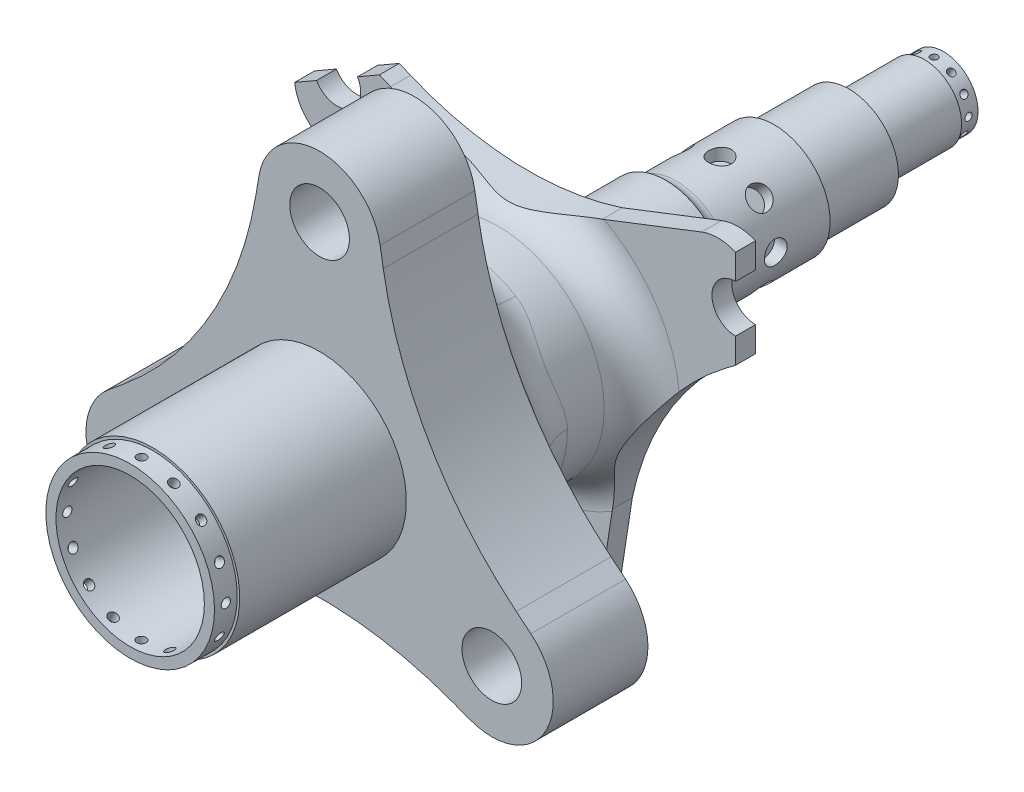
SolidWorks part; units mm, degrees
ref_plane "Front Plane" through (0, 0, 0) normal (0, 0, 1) x (1, 0, 0)
ref_plane "Top Plane" through (0, 0, 0) normal (0, 1, 0) x (1, 0, 0)
ref_plane "Right Plane" through (0, 0, 0) normal (1, 0, 0) x (0, 0, -1)
sketch "Sketch1" plane through (0, 0, 0) normal (0, 0, 1) x (1, 0, 0)
  circle A0 centre (0, 0) radius 10
  dimension "D1" = 20
extrude "IB mount" add sketch "Sketch1" along normal mid plane 15
ref_plane "OB midplane" through (0, 0, 36.83) normal (0, 0, 1) x (1, 0, 0)
sketch "Sketch2" plane through (0, 0, 36.83) normal (0, 0, 1) x (1, 0, 0)
  circle A0 centre (0, 0) radius 12.5
  dimension "D1" = 25
extrude "OB mount" add sketch "Sketch2" along normal mid plane 15 separate body contours A0
ref_plane "Rotor midplane" through (0, 0, 53.34) normal (0, 0, 1) x (1, 0, 0)
sketch "Sketch4" plane through (0, 0, 53.34) normal (0, 0, 1) x (1, 0, 0)
  circle A0 centre (0, 0) radius 82.55
  dimension "D1" = 165.1
extrude "Boss-Extrude3" add sketch "Sketch4" along normal mid plane 4 separate body contours A0
ref_plane "Wheel Center Midplane" through (0, 0, 89.408) normal (0, 0, 1) x (1, 0, 0)
sketch "Sketch5" plane through (0, 0, 89.408) normal (0, 0, 1) x (1, 0, 0)
  line L0 (-19.4328, 52.35) -> (18.1305, 52.35) construction
  line L1 (-19.4328, 46) -> (18.1305, 46) construction
  circle A0 centre (0, 0) radius 52.35
  circle A1 centre (0, 40) radius 6
  circle A2 centre (20, 34.641) radius 6
  circle A3 centre (34.641, 20) radius 6
  circle A4 centre (40, 0) radius 6
  circle A5 centre (34.641, -20) radius 6
  circle A6 centre (20, -34.641) radius 6
  circle A7 centre (0, -40) radius 6
  circle A8 centre (-20, -34.641) radius 6
  circle A9 centre (-34.641, -20) radius 6
  circle A10 centre (-40, 0) radius 6
  circle A11 centre (-34.641, 20) radius 6
  circle A12 centre (-20, 34.641) radius 6
  point P29 (0, 0)
  dimension "D3" = 12
  dimension "D2" = 40
  dimension "D4" = 6.35
  dimension "D1" = 12
extrude "Boss-Extrude4" add sketch "Sketch5" along normal mid plane 19.05 separate body contours A0 A12 A11 A10 A9 A8 A7 A6 A5 A4 A3 A2 A1 | A12 | A1 | A2 | A3 | A4 | A5 | A6 | A7 | A8 | A9 | A10 | A11 region at (0, 0, 89.408) region at (0, 40, 89.408) region at (20, 34.641, 89.408) region at (34.641, 20, 89.408) region at (40, 0, 89.408) region at (34.641, -20, 89.408) region at (20, -34.641, 89.408) region at (0, -40, 89.408) region at (-20, -34.641, 89.408) region at (-34.641, -20, 89.408) region at (-40, 0, 89.408) region at (-34.641, 20, 89.408) region at (-20, 34.641, 89.408)
extrude "Cut-Extrude2" cut sketch "Sketch5<5>" against normal blind 19.05 from surface contours A1 | A5 | A9 starting at face at (52.35, 0, 98.933)
sketch "Sketch5<5>" plane through (0, 0, 89.408) normal (0, 0, 1) x (1, 0, 0) same geometry as "Sketch5"
sketch "Sketch8" plane through (0, 0, 98.933) normal (0, 0, 1) x (1, 0, 0)
  circle A0 centre (0, 0) radius 17.4625
  dimension "D1" = 34.925
extrude "Boss-Extrude5" add sketch "Sketch8" along normal blind 38.1
sketch "Sketch9" plane through (0, 0, 137.033) normal (0, 0, 1) x (1, 0, 0)
  circle A0 centre (0, 0) radius 14.9225
  dimension "D1" = 29.845
sketch "Sketch10" plane through (0, 0, 29.33) normal (0, 0, -1) x (-1, 0, 0)
  circle A2 centre (0, 0) radius 11.25
  circle A3 centre (0, 0) radius 11.25
  dimension "D1" = 1.25
extrude "Boss-Extrude6" add sketch "Sketch10" along normal up to surface (21.83 mm away) up to face at (10, 0, 7.5)
sketch "Sketch11" plane through (0, 0, 0) normal (0, 1, 0) x (1, 0, 0)
  line L2 (11.25, -7.5) -> (-11.25, -7.5) construction
  line L3 (11.25, -7.5) -> (-11.25, -7.5) construction
  line L4 (0, -29.33) -> (0, -7.5) construction
  line L6 (12.5, -29.33) -> (-12.5, -29.33) construction
  line L7 (12.5, -29.33) -> (-12.5, -29.33) construction
  circle A0 centre (0, -18.415) radius 2.286
  dimension "D1" = 4.572
ref_plane "WS sensor plane" through (0, 11.25, 0) normal (0, 1, 0) x (1, 0, 0)
sketch "Sketch12" plane through (0, 11.25, 0) normal (0, 1, 0) x (1, 0, 0)
  circle A0 centre (0, -18.415) radius 2.286
  circle A1 centre (0, -18.415) radius 2.286 construction
extrude "Cut-Extrude4" cut sketch "Sketch12" against normal blind 2.54 contours A0
pattern_circular "CirPattern1" count 8 over 360 about axis through (0, 0, -7.5) along (0, 0, -1) of "Cut-Extrude4"
sketch "Sketch15" plane through (0, 0, 79.883) normal (0, 0, -1) x (-1, 0, 0)
  circle A2 centre (0, 0) radius 21.2725
  circle A3 centre (0, 0) radius 21.2725
  dimension "D1" = 3.81
extrude "Boss-Extrude7" add sketch "Sketch15" along normal up to surface (24.543 mm away) contours A3 up to face at (82.55, 0, 55.34)
extrude "Cut-Extrude5" cut sketch "Sketch9" against normal up to surface (47.625 mm away) contours A0 up to plane "Wheel Center Midplane"
sketch "Sketch16" plane through (0, 0, 44.33) normal (0, 0, 1) x (1, 0, 0)
  circle A2 centre (0, 0) radius 15
  circle A3 centre (0, 0) radius 15
  dimension "D1" = 2.5
extrude "Boss-Extrude8" add sketch "Sketch16" along normal up to surface (7.01 mm away) up to face at (82.55, 0, 51.34)
fillet "Fillet4" radius 3.81 1 edges at (15, 0, 51.34)
sketch "Sketch17" plane through (0, 0, -7.5) normal (0, 0, -1) x (-1, 0, 0)
  circle A3 centre (0, 0) radius 7.46
  circle A4 centre (0, 0) radius 7.46
  dimension "D2" = 14.92
  dimension "D1" = 2.54
extrude "Boss-Extrude9" add sketch "Sketch17" along normal blind 19.05 contours A4
sketch "Sketch18" plane through (0, 0, -26.55) normal (0, 0, -1) x (-1, 0, 0)
  circle A2 centre (0, 0) radius 4.92
  circle A3 centre (0, 0) radius 4.92
  dimension "D1" = 2.54
extrude "Cut-Extrude6" cut sketch "Sketch18" against normal blind 3.81
sketch "Sketch19" plane through (0, 0, -26.55) normal (0, 0, -1) x (-1, 0, 0)
  circle A1 centre (0, 0) radius 7.46
  circle A2 centre (0, 0) radius 6.96
  circle A3 centre (0, 0) radius 6.96
  dimension "D1" = 0.5
extrude "Cut-Extrude7" cut sketch "Sketch19" against normal up to surface (3.81 mm away) up to face at (-4.92, 0, -22.74)
ref_plane "Plane5" through (0, 6.96, 0) normal (0, 1, 0) x (1, 0, 0)
sketch "Sketch20" plane through (0, 6.96, 0) normal (0, 1, 0) x (1, 0, 0)
  line L0 (6.96, 26.55) -> (-6.96, 26.55) construction
  line L1 (6.96, 26.55) -> (-6.96, 26.55) construction
  line L2 (6.96, 22.74) -> (-6.96, 22.74) construction
  line L3 (6.96, 22.74) -> (-6.96, 22.74) construction
  line L4 (0, 22.74) -> (0, 26.55) construction
  circle A0 centre (0, 24.645) radius 0.7319
extrude "Cut-Extrude8" cut sketch "Sketch20" against normal up to surface and the other way through all up to face at (-4.92, 0, -22.74)
pattern_circular "CirPattern2" count 12 over 360 about axis through (0, 0, -26.55) along (0, 0, -1) of "Cut-Extrude8"
sketch "Sketch21" plane through (0, 0, 137.033) normal (0, 0, 1) x (1, 0, 0)
  circle A1 centre (0, 0) radius 17.4625
  circle A2 centre (0, 0) radius 16.9625
  circle A3 centre (0, 0) radius 16.9625
  circle M3 centre (0, 0) radius 17.4625
  dimension "D1" = 0.5
extrude "Cut-Extrude9" cut sketch "Sketch21" against normal blind 4.572 contours A3 M3 region at (-16.9686, 0, 137.033)
sketch "Sketch22" plane through (0, 0, 0) normal (0, 1, 0) x (1, 0, 0)
  line L0 (-16.9625, -137.033) -> (16.9625, -137.033) construction
  line L1 (-16.9625, -132.461) -> (16.9625, -132.461) construction
  line L2 (-16.9625, -137.033) -> (16.9625, -137.033) construction
  line L3 (-16.9625, -132.461) -> (16.9625, -132.461) construction
  line L4 (0, -132.461) -> (0, -137.033) construction
  circle A0 centre (0, -134.747) radius 0.9339
extrude "Cut-Extrude10" cut sketch "Sketch22" against normal up to surface (16.9625 mm away) up to face at (16.9625, 0, 132.461)
pattern_circular "CirPattern3" count 16 over 360 about axis through (0, 0, 137.033) along (0, 0, 1) of "Cut-Extrude10"
sketch "Brakes Rough Diagram" plane through (0, 0, 51.34) normal (0, 0, -1) x (-1, 0, 0)
  line L0 (-31.719, 82.55) -> (31.719, 82.55) construction
  line L5 (-22.9, 82.05) -> (22.9, 82.05)
  line L6 (-22.9, 82.05) -> (-22.9, 53.55)
  line L7 (-22.9, 53.55) -> (22.9, 53.55)
  line L8 (22.9, 82.05) -> (22.9, 53.55)
  line L9 (-31.719, 53.05) -> (31.719, 53.05) construction
  line L10 (-31.719, 51.05) -> (31.719, 51.05) construction
  line L11 (-22.9, 82.05) -> (22.9, 53.55) construction
  line L12 (-22.9, 53.55) -> (22.9, 82.05) construction
  circle A0 centre (0, 0) radius 53.05 construction
  circle A1 centre (0, 0) radius 82.55 construction
  circle A2 centre (0, 46.2875) radius 4.7625
  point P16 (0, 67.8)
  point P17 (0, 67.8)
  point P22 (0, 51.05)
  point P24 (0, 53.55)
  point P25 (0, 53.05)
  dimension "D6" = 9.525
  dimension "D1" = 28.5
  dimension "D2" = 45.8
  dimension "D3" = 0.5
  dimension "D4" = 0.5
  dimension "D5" = 2
sketch "Sketch28" plane through (0, 0, 51.34) normal (0, 0, -1) x (-1, 0, 0)
  circle A0 centre (0, 46.2875) radius 4.7625 construction
  circle A1 centre (0, 46.2875) radius 4.7625
  circle A2 centre (23.1437, 40.0862) radius 4.7625
  circle A3 centre (40.0862, 23.1438) radius 4.7625
  circle A4 centre (46.2875, 0) radius 4.7625
  circle A5 centre (40.0862, -23.1437) radius 4.7625
  circle A6 centre (23.1438, -40.0862) radius 4.7625
  circle A7 centre (0, -46.2875) radius 4.7625
  circle A8 centre (-23.1437, -40.0862) radius 4.7625
  circle A9 centre (-40.0862, -23.1438) radius 4.7625
  circle A10 centre (-46.2875, 0) radius 4.7625
  circle A11 centre (-40.0862, 23.1437) radius 4.7625
  circle A12 centre (-23.1438, 40.0862) radius 4.7625
  circle A13 centre (0, 0) radius 53.05 construction
  circle A14 centre (0, 0) radius 53.05
  circle A16 centre (0, 0) radius 82.55
  circle A17 centre (0, 0) radius 82.55
  point P27 (0, 0)
  circle M6 centre (0, 0) radius 82.55
  dimension "D2" = 0
  dimension "D1" = 12
extrude "Cut-Extrude11" cut sketch "Sketch28" along direction (0, 0, 1) on the side against the normal up to surface (4 mm away) contours A14 M6 | A3 | A11 | A7 region at (-40.0862, 23.1438, 51.34) region at (0, -46.2875, 51.34) region at (40.0862, 23.1437, 51.34) region at (80.2151, 0, 51.34) up to face at (21.2725, 0, 55.34)
sketch "Brake Rotor Mount Points" plane through (0, 0, 51.34) normal (0, 0, -1) x (-1, 0, 0)
  line L0 (-4.7625, 46.2875) -> (4.7625, 46.2875) construction
  line L1 (-4.1244, 43.9062) -> (4.1244, 48.6688) construction
  line L2 (0, 51.05) -> (0, 41.525) construction
  line L3 (4.1244, 48.6688) -> (8.5239, 51.2088)
  line L4 (-4.1244, 43.9062) -> (-8.5239, 41.3662)
  line L5 (18.3812, 40.0862) -> (27.9062, 40.0862) construction
  line L6 (19.0193, 42.4674) -> (27.2682, 37.7049) construction
  line L7 (25.525, 44.2106) -> (20.7625, 35.9617) construction
  line L8 (27.9062, 40.0862) -> (32.9862, 40.0862)
  line L9 (18.3812, 40.0862) -> (13.3012, 40.0862)
  line L10 (35.9617, 25.525) -> (44.2106, 20.7625) construction
  line L11 (37.7049, 27.2682) -> (42.4674, 19.0193) construction
  line L12 (44.2106, 25.525) -> (35.9617, 20.7625) construction
  line L13 (44.2106, 20.7625) -> (48.61, 18.2225)
  line L14 (35.9617, 25.525) -> (31.5623, 28.065)
  line L15 (43.9062, 4.1244) -> (48.6688, -4.1244) construction
  line L16 (46.2875, 4.7625) -> (46.2875, -4.7625) construction
  line L17 (51.05, 0) -> (41.525, 0) construction
  line L18 (48.6688, -4.1244) -> (51.2088, -8.5239)
  line L19 (43.9062, 4.1244) -> (41.3662, 8.5239)
  line L20 (40.0862, -18.3812) -> (40.0862, -27.9062) construction
  line L21 (42.4674, -19.0193) -> (37.7049, -27.2682) construction
  line L22 (44.2106, -25.525) -> (35.9617, -20.7625) construction
  line L23 (40.0862, -27.9062) -> (40.0862, -32.9862)
  line L24 (40.0862, -18.3812) -> (40.0862, -13.3012)
  line L25 (25.525, -35.9617) -> (20.7625, -44.2106) construction
  line L26 (27.2682, -37.7049) -> (19.0193, -42.4674) construction
  line L27 (25.525, -44.2106) -> (20.7625, -35.9617) construction
  line L28 (20.7625, -44.2106) -> (18.2225, -48.61)
  line L29 (25.525, -35.9617) -> (28.065, -31.5623)
  line L30 (4.1244, -43.9062) -> (-4.1244, -48.6688) construction
  line L31 (4.7625, -46.2875) -> (-4.7625, -46.2875) construction
  line L32 (0, -51.05) -> (0, -41.525) construction
  line L33 (-4.1244, -48.6688) -> (-8.5239, -51.2088)
  line L34 (4.1244, -43.9062) -> (8.5239, -41.3662)
  line L35 (-18.3812, -40.0862) -> (-27.9062, -40.0862) construction
  line L36 (-19.0193, -42.4674) -> (-27.2682, -37.7049) construction
  line L37 (-25.525, -44.2106) -> (-20.7625, -35.9617) construction
  line L38 (-27.9062, -40.0862) -> (-32.9862, -40.0862)
  line L39 (-18.3812, -40.0862) -> (-13.3012, -40.0862)
  line L40 (-35.9617, -25.525) -> (-44.2106, -20.7625) construction
  line L41 (-37.7049, -27.2682) -> (-42.4674, -19.0193) construction
  line L42 (-44.2106, -25.525) -> (-35.9617, -20.7625) construction
  line L43 (-44.2106, -20.7625) -> (-48.61, -18.2225)
  line L44 (-35.9617, -25.525) -> (-31.5623, -28.065)
  line L45 (-43.9062, -4.1244) -> (-48.6688, 4.1244) construction
  line L46 (-46.2875, -4.7625) -> (-46.2875, 4.7625) construction
  line L47 (-51.05, 0) -> (-41.525, 0) construction
  line L48 (-48.6688, 4.1244) -> (-51.2088, 8.5239)
  line L49 (-43.9062, -4.1244) -> (-41.3662, -8.5239)
  line L50 (-40.0862, 18.3812) -> (-40.0862, 27.9062) construction
  line L51 (-42.4674, 19.0193) -> (-37.7049, 27.2682) construction
  line L52 (-44.2106, 25.525) -> (-35.9617, 20.7625) construction
  line L53 (-40.0862, 27.9062) -> (-40.0862, 32.9862)
  line L54 (-40.0862, 18.3812) -> (-40.0862, 13.3012)
  line L55 (-25.525, 35.9617) -> (-20.7625, 44.2106) construction
  line L56 (-27.2682, 37.7049) -> (-19.0193, 42.4674) construction
  line L57 (-25.525, 44.2106) -> (-20.7625, 35.9617) construction
  line L58 (-20.7625, 44.2106) -> (-18.2225, 48.61)
  line L59 (-25.525, 35.9617) -> (-28.065, 31.5623)
  circle A1 centre (23.1438, -40.0862) radius 4.7625
  circle A2 centre (23.1438, -40.0862) radius 4.7625 construction
  circle A3 centre (40.0862, -23.1437) radius 4.7625
  circle A4 centre (40.0862, -23.1437) radius 4.7625 construction
  circle A5 centre (46.2875, 0) radius 4.7625
  circle A6 centre (46.2875, 0) radius 4.7625 construction
  circle A7 centre (40.0862, 23.1438) radius 4.7625
  circle A8 centre (40.0862, 23.1438) radius 4.7625 construction
  circle A9 centre (23.1437, 40.0862) radius 4.7625
  circle A10 centre (23.1437, 40.0862) radius 4.7625 construction
  circle A11 centre (0, 46.2875) radius 4.7625
  circle A12 centre (0, 46.2875) radius 4.7625 construction
  circle A13 centre (0, 0) radius 53.05
  circle A14 centre (0, 0) radius 53.05 construction
  circle A15 centre (-23.1438, 40.0862) radius 4.7625
  circle A16 centre (-23.1438, 40.0862) radius 4.7625 construction
  circle A17 centre (-40.0862, 23.1437) radius 4.7625
  circle A18 centre (-40.0862, 23.1437) radius 4.7625 construction
  circle A19 centre (-46.2875, 0) radius 4.7625
  circle A20 centre (-46.2875, 0) radius 4.7625 construction
  circle A21 centre (-40.0862, -23.1438) radius 4.7625
  circle A22 centre (-40.0862, -23.1438) radius 4.7625 construction
  circle A23 centre (-23.1437, -40.0862) radius 4.7625
  circle A24 centre (-23.1437, -40.0862) radius 4.7625 construction
  circle A25 centre (0, -46.2875) radius 4.7625
  circle A26 centre (0, -46.2875) radius 4.7625 construction
  circle A27 centre (0, 0) radius 82.55
  circle A28 centre (0, 0) radius 82.55 construction
  point P140 (0, 0)
  dimension "D15" = 60
  dimension "D17" = 5.08
  dimension "D1" = 0
  dimension "D2" = 0
  dimension "D3" = 0
  dimension "D4" = 0
  dimension "D5" = 0
  dimension "D6" = 0
  dimension "D7" = 0
  dimension "D8" = 0
  dimension "D9" = 0
  dimension "D10" = 0
  dimension "D11" = 0
  dimension "D12" = 0
  dimension "D13" = 0
  dimension "D14" = 0
  dimension "D16" = 12
sketch "Sketch30" plane through (0, 0, 51.34) normal (0, 0, -1) x (-1, 0, 0)
  line L0 (-4.1244, -48.6688) -> (-8.5239, -51.2088) construction
  line L1 (4.1244, -43.9062) -> (8.5239, -41.3662) construction
  line L2 (35.9617, 25.525) -> (31.5623, 28.065) construction
  line L3 (44.2106, 20.7625) -> (48.61, 18.2225) construction
  line L4 (-40.0862, 18.3812) -> (-40.0862, 13.3012) construction
  line L5 (-40.0862, 27.9062) -> (-40.0862, 32.9862) construction
  line L6 (-4.1244, -48.6688) -> (-8.5239, -51.2088)
  line L7 (4.1244, -43.9062) -> (8.5239, -41.3662)
  line L8 (35.9617, 25.525) -> (31.5623, 28.065)
  line L9 (44.2106, 20.7625) -> (48.61, 18.2225)
  line L10 (-40.0862, 18.3812) -> (-40.0862, 13.3012)
  line L11 (-40.0862, 27.9062) -> (-40.0862, 32.9862)
  line L12 (-40.0862, 13.3012) -> (-18.5757, -2.9599)
  line L13 (-33.2561, 33.0986) -> (6.7245, 17.5669)
  line L14 (45.2923, 12.2513) -> (11.8512, -14.607)
  line L15 (31.5623, 28.065) -> (6.7245, 17.5669)
  line L16 (-12.0362, -45.3499) -> (-18.5757, -2.9599)
  line L17 (8.5239, -41.3662) -> (11.8512, -14.607)
  line L18 (-12.0362, -45.3499) -> (-18.5757, -2.9599)
  line L19 (-33.2561, 33.0986) -> (6.7245, 17.5669)
  circle A0 centre (0, -46.2875) radius 4.7625 construction
  circle A1 centre (40.0862, 23.1438) radius 4.7625 construction
  circle A2 centre (-40.0862, 23.1437) radius 4.7625 construction
  circle A3 centre (0, -46.2875) radius 4.7625
  circle A4 centre (40.0862, 23.1438) radius 4.7625
  circle A5 centre (-40.0862, 23.1437) radius 4.7625
  arc A6 (-40.0862, 32.9862) -> (-33.2561, 33.0986) centre (-36.5332, 24.6629) cw
  circle A7 centre (0, 0) radius 18.81 construction
  arc A8 (48.61, 18.2225) -> (45.2923, 12.2513) centre (39.6253, 19.3073) cw
  arc A9 (-8.5239, -51.2088) -> (-12.0362, -45.3499) centre (-3.092, -43.9701) cw
  circle A10 centre (0, 0) radius 53.05 construction
  circle A11 centre (0, 0) radius 53.05
  arc A12 (8.825, -38.9441) -> (28.5717, -1.1779) centre (69.1617, -46.4466) cw
  arc A13 (-38.1391, 11.8294) -> (-15.3059, -24.1549) centre (-74.8047, -36.6725) cw
  arc A14 (29.3141, 27.1148) -> (-13.2658, 25.3328) centre (5.6431, 83.119) cw
  point P42 (0, 0)
  point P52 (0, 0)
  circle M2 centre (0, -46.2875) radius 4.7625
  circle M3 centre (-40.0862, 23.1437) radius 4.7625
  circle M4 centre (40.0862, 23.1438) radius 4.7625
  circle M6 centre (0, 0) radius 53.05
  dimension "D1" = 3
  dimension "D2" = 3
extrude "Cut-Extrude12" cut sketch "Sketch30" against normal up to surface (4 mm away) contours L6 A9 L16 L12 L10 L11 A6 L13 L15 L8 L9 A8 L14 L17 L7 M6 M3 M4 M2 region at (51.5495, 0, 51.34) up to face at (4.7625, -46.2875, 55.34)
fillet "Fillet5" radius 7.62 1 edges at (21.2725, 0, 55.34)
ref_axis "Axis1" through (0, 0, 162.3917) along (0, 0, -1)
ref_point "Point1"
sketch "Sketch32" plane through (0, 0, 98.933) normal (0, 0, 1) x (1, 0, 0)
  line L0 (0, 0) -> (0, 80.8736) construction
  line L1 (0, 0) -> (83.8458, 48.4084) construction
  line L2 (18.8828, 18.0941) -> (21.997, 12.7) construction
  line L3 (12.1803, 42.0402) -> (12.8097, 38.2826)
  line L4 (-12.1803, 42.0402) -> (-12.8097, 38.2826)
  line L5 (30.3177, -31.5686) -> (26.7488, -30.2348)
  line L6 (42.4981, -10.4717) -> (39.5585, -8.0477)
  line L7 (-42.4981, -10.4717) -> (-39.5585, -8.0477)
  line L8 (-30.3177, -31.5686) -> (-26.7488, -30.2348)
  arc A0 (-12.1803, 42.0402) -> (12.1803, 42.0402) centre (0, 40) cw
  arc A1 (21.997, 12.7) -> (12.8097, 38.2826) centre (88.1714, 50.9058) cw
  circle A2 centre (0, 40) radius 6 construction
  circle A3 centre (0, 0) radius 52.35 construction
  arc A4 (-21.997, 12.7) -> (-12.8097, 38.2826) centre (-88.1714, 50.9058) ccw
  arc A5 (42.4981, -10.4717) -> (30.3177, -31.5686) centre (34.641, -20) cw
  arc A6 (21.997, 12.7) -> (39.5585, -8.0477) centre (88.1714, 50.9058) ccw
  arc A7 (0, -25.4) -> (26.7488, -30.2348) centre (0, -101.8116) cw
  arc A8 (-30.3177, -31.5686) -> (-42.4981, -10.4717) centre (-34.641, -20) cw
  arc A9 (0, -25.4) -> (-26.7488, -30.2348) centre (0, -101.8116) ccw
  arc A10 (-21.997, 12.7) -> (-39.5585, -8.0477) centre (-88.1714, 50.9058) cw
  circle A12 centre (0, 0) radius 52.35
  circle A13 centre (0, 0) radius 52.35
  point P38 (0, 0)
  circle M9 centre (0, 0) radius 52.35
  dimension "D1" = 60
  dimension "D2" = 25.4
  dimension "D3" = 3.81
  dimension "D5" = 0
  dimension "D4" = 3
extrude "Cut-Extrude13" cut sketch "Sketch32" against normal up to surface (19.05 mm away) contours A1 A6 L6 A5 A0 L3 M9 | A10 A4 L4 A0 A8 L7 M9 | A7 A9 L8 A8 A5 L5 M9 region at (33.0556, 19.0847, 98.933) region at (-33.0556, 19.0847, 98.933) region at (0, -38.1694, 98.933) up to face at (-21.2725, 0, 79.883)
fillet "Fillet3" radius 9.525 1 edges at (-21.2725, 0, 79.883)
fillet "Fillet7" radius 2.54 1 edges at (-11.25, 0, 29.33)
equation "\"Frotor\"= 1198.79'inches; approximate value at brake pad"
equation "\"Floatpin_dist\"= 1.8223'inches; dist from float pins to central axis"
equation "\"Torque_rotor\"= \"Frotor\" * \"Floatpin_dist\"'Torque in lb*in of brakes acting on brake rotor mount"
